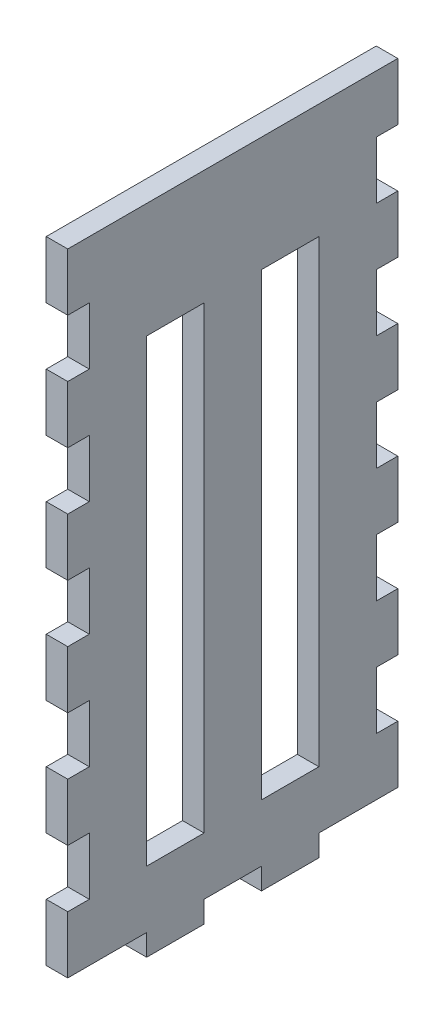
SolidWorks part; units mm, degrees
ref_plane "Front Plane" through (0, 0, 0) normal (0, 0, 1) x (1, 0, 0)
ref_plane "Top Plane" through (0, 0, 0) normal (0, 1, 0) x (1, 0, 0)
ref_plane "Right Plane" through (0, 0, 0) normal (1, 0, 0) x (0, 0, -1)
sketch "Sketch1" plane through (0, 0, 0) normal (1, 0, 0) x (0, 0, -1)
  line L1 (-63.5, -139.7) -> (63.5, -139.7)
  line L2 (-63.5, -139.7) -> (-63.5, 139.7)
  line L3 (-63.5, 139.7) -> (63.5, 139.7)
  line L4 (63.5, -139.7) -> (63.5, 139.7)
  line L5 (-63.5, -139.7) -> (63.5, 139.7) construction
  line L6 (-63.5, 139.7) -> (63.5, -139.7) construction
  point P0 (0, 0)
  dimension "D1" = 127
  dimension "D2" = 279.4
extrude "Boss-Extrude1" add sketch "Sketch1" along normal blind 9.525
sketch "Sketch2" plane through (0, 0, 63.5) normal (0, 0, 1) x (1, 0, 0)
  line L0 (0, 139.7) -> (0, -139.7) construction
  line L1 (0, 139.7) -> (9.525, 139.7)
  line L2 (0, 139.7) -> (0, 114.3)
  line L3 (0, 114.3) -> (9.525, 114.3)
  line L4 (9.525, 139.7) -> (9.525, 114.3)
  line L5 (0, -69.85) -> (0, 69.85) construction
  line L6 (9.525, 139.7) -> (9.525, -139.7) construction
  line L7 (9.525, 139.7) -> (0, 139.7) construction
  dimension "D1" = 25.4
  dimension "D2" = 0
extrude "Boss-Extrude2" add sketch "Sketch2" along normal blind 9.525
pattern_linear "LPattern1" count 6 spacing 50.8 along (0, -1, 0) of "Boss-Extrude2"
mirror "Mirror1" about plane through (0, 0, 0) normal (0, 0, 1) of "LPattern1"
sketch "Sketch3" plane through (0, -139.7, 0) normal (0, -1, 0) x (1, 0, 0)
  line L0 (0, 73.025) -> (0, -73.025) construction
  line L1 (0, 38.1) -> (9.525, 38.1)
  line L2 (0, 38.1) -> (0, 12.7)
  line L3 (0, 12.7) -> (9.525, 12.7)
  line L4 (9.525, 38.1) -> (9.525, 12.7)
  line L5 (9.525, 73.025) -> (9.525, -73.025) construction
  line L6 (0, 73.025) -> (9.525, 73.025) construction
  dimension "D1" = 34.925
  dimension "D2" = 25.4
extrude "Boss-Extrude3" add sketch "Sketch3" along normal blind 9.525
pattern_linear "LPattern2" count 2 spacing 50.8 along (0, 0, -1) of "Boss-Extrude3"
sketch "Sketch4" plane through (9.525, 0, 0) normal (1, 0, 0) x (0, 0, -1)
  line L0 (-38.1, -149.225) -> (-38.1, -139.7) construction
  line L1 (-38.1, -114.3) -> (-12.7, -114.3)
  line L2 (-38.1, -114.3) -> (-38.1, 88.9)
  line L3 (-38.1, 88.9) -> (-12.7, 88.9)
  line L4 (-12.7, -114.3) -> (-12.7, 88.9)
  line L5 (-73.025, -139.7) -> (-38.1, -139.7) construction
  line L6 (-73.025, 88.9) -> (-63.5, 88.9) construction
  point P10 (-68.2625, 88.9)
  dimension "D1" = 0
  dimension "D2" = 25.4
  dimension "D3" = 25.4
  dimension "D4" = 0
extrude "Cut-Extrude1" cut sketch "Sketch4" against normal blind 9.525
mirror "Mirror2" about plane through (0, 0, 0) normal (0, 0, 1) of "Cut-Extrude1"
